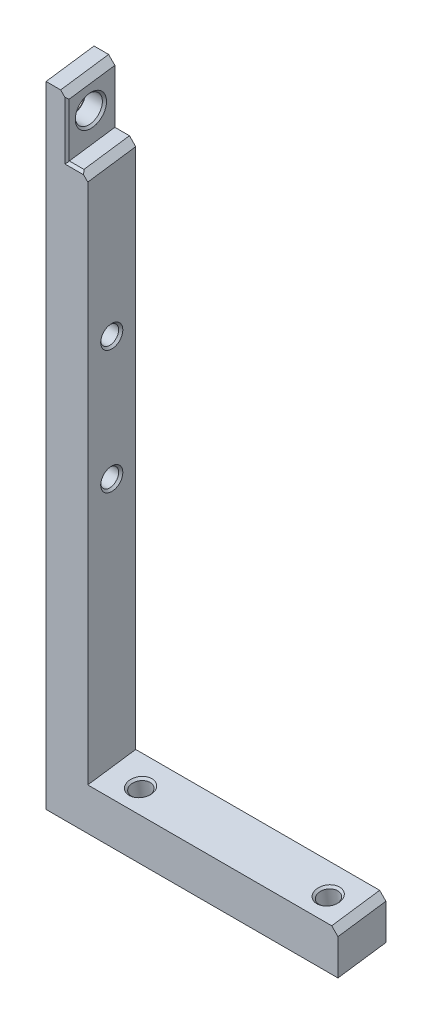
SolidWorks part; units mm, degrees
ref_plane "Top" through (0, 0, 0) normal (0, 0, 1) x (1, 0, 0)
ref_plane "Front" through (0, 0, 0) normal (0, 1, 0) x (1, 0, 0)
ref_plane "Right" through (0, 0, 0) normal (1, 0, 0) x (0, 0, -1)
sketch "Sketch4" plane through (0, 0, 0) normal (1, 0, 0) x (0, 0, -1)
  line L1 (0, 0) -> (11.5, 0)
  line L2 (0, 0) -> (0, 144)
  line L3 (0, 144) -> (11.5, 144)
  line L4 (11.5, 0) -> (11.5, 144)
  dimension "D1" = 11.5
  dimension "D2" = 144
extrude "Boss-Extrude2" add sketch "Sketch4" along normal blind 10
sketch "Sketch6" plane through (10, 0, 0) normal (1, 0, 0) x (0, 0, -1)
  line L0 (5.75, 0) -> (11.5, 0.8081)
  line L1 (0, 0) -> (11.5, 0) construction
  line L2 (11.5, 0) -> (11.5, 144) construction
  line L3 (11.5, 0.8081) -> (10.1083, 10.7108)
  line L4 (10.1083, 10.7108) -> (0.2056, 9.3191)
  line L5 (0.2056, 9.3191) -> (1.5973, -0.5836)
  line L6 (1.5973, -0.5836) -> (5.75, 0)
  line L7 (0, 144) -> (0, 0) construction
  dimension "D1" = 10
  dimension "D2" = 10
  dimension "D3" = 82
extrude "Boss-Extrude3" add sketch "Sketch6" along normal blind 60 and the other way blind 10
sketch "Sketch7" plane through (10, 0, 0) normal (1, 0, 0) x (0, 0, -1)
  line L0 (-3.1126, -1.2456) -> (11.8209, -3.029)
  line L2 (11.8209, -3.029) -> (11.8209, 0.8532)
  line L3 (11.8209, 0.8532) -> (-3.1126, -1.2456)
  line L4 (1.5973, -0.5836) -> (11.5, 0.8081) construction
extrude "Cut-Extrude2" cut sketch "Sketch7" against normal blind 10
sketch "Sketch8" plane through (0, 9.1102, 1.2804) normal (0, 0.9903, 0.1392) x (1, 0, 0)
  line L0 (10, 1.5005) -> (70, 1.5005) construction
  line L1 (70, 11.5005) -> (70, 1.5005) construction
  circle A0 centre (62.5, 6.5005) radius 2.25
  circle A1 centre (17.5, 6.5005) radius 2.25
  dimension "D2" = 4.5
  dimension "D3" = 4.5
  dimension "D1" = 45
  dimension "D4" = 5
  dimension "D5" = 7.5
extrude "Cut-Extrude3" cut sketch "Sketch8" against normal blind 10
sketch "Sketch11" plane through (0, 9.1102, 1.2804) normal (0, 0.9903, 0.1392) x (1, 0, 0)
  line L0 (13.5, 6.5005) -> (13.5, 0)
  line L1 (13.5, 0) -> (21.5, 0)
  line L3 (21.5, 0) -> (21.5, 6.5005)
  line L4 (10, 0) -> (0, 0) construction
  circle A0 centre (17.5, 6.5005) radius 4 construction
  arc A1 (21.5, 6.5005) -> (13.5, 6.5005) centre (17.5, 6.5005) ccw
  dimension "D1" = 8
sketch "Sketch12" plane through (70, 0, 0) normal (1, 0, 0) x (0, 0, -1)
  line L5 (0.2056, 9.3191) -> (10.1083, 10.7108) construction
  line L13 (1.5973, -0.5836) -> (0, -0.8081)
  line L14 (0, -0.8081) -> (0, 9.2902)
  line L16 (1.5973, -0.5836) -> (11.5, 0.8081) construction
  line L17 (0, 144) -> (0, 0) construction
  line L18 (11.5, 0.8081) -> (11.5, 10.9064)
  line L20 (11.5, 10.9064) -> (10.1083, 10.7108)
  line L21 (10.1083, 10.7108) -> (11.5, 0.8081)
  line L22 (10.1083, 10.7108) -> (0.2056, 9.3191) construction
  line L23 (11.5, 0.8081) -> (11.5, 144) construction
  line L25 (11.5, 0.8081) -> (10.1083, 10.7108) construction
  line L26 (0, 9.2902) -> (0.2056, 9.3191)
  line L27 (0.2056, 9.3191) -> (1.5973, -0.5836)
  line L28 (0.2056, 9.3191) -> (1.5973, -0.5836) construction
extrude "Boss-Extrude4" add sketch "Sketch12" against normal up to surface (70 mm away) up to face at (0, 48.0374, -4.3521)
sketch "Sketch13" plane through (10, 0, 0) normal (1, 0, 0) x (0, 0, -1)
  line L0 (11.5, 144) -> (11.5, 152)
  line L1 (11.5, 152) -> (0, 150.3838)
  line L2 (0, 150.3838) -> (0, 144)
  line L3 (0, 144) -> (11.5, 144)
  line L4 (11.5, 10.9064) -> (0, 9.2902) construction
  dimension "D1" = 8
extrude "Boss-Extrude5" add sketch "Sketch13" against normal blind 10
sketch "Sketch14" plane through (10, 0, 0) normal (1, 0, 0) x (0, 0, -1)
  line L0 (11.5, 10.9064) -> (11.5, 152) construction
  circle A0 centre (5.75, 144) radius 3.25
  dimension "D2" = 6.5
  dimension "D1" = 8
  dimension "D3" = 5.75
extrude "Cut-Extrude5" cut sketch "Sketch14" against normal blind 10
sketch "Sketch18" plane through (10, 0, 0) normal (1, 0, 0) x (0, 0, -1)
  line L0 (5.75, 99.6) -> (5.75, 70)
  line L1 (11.5, 10.9064) -> (11.5, 152) construction
  dimension "D1" = 5.75
  dimension "D2" = 29.6
  dimension "D3" = 70
hole_wizard "M4 Clearance Hole1" positions "Sketch19" profile "Sketch20" hole size "M4" standard "DIN" end condition through all
sketch "Sketch19" plane through (10, 0, 0) normal (1, 0, 0) x (0, 0, -1)
  point P0 (5.75, 70)
  point P3 (5.75, 99.6)
sketch "Sketch20" plane through (10, 70, -5.75) normal (0, 1, 0) x (0, 0, -1)
  line L0 (0, 0) -> (0, 10)
  line L1 (0, 10) -> (2.15, 10)
  line L2 (2.15, 10) -> (2.15, 0)
  line L5 (2.15, 0) -> (0, 0)
  line L11 (0, -6.35) -> (0, 107.95) construction
  dimension "Thru Hole Dia." = 4.3
  dimension "Thru Hole Depth" = 10
sketch "Sketch24" plane through (10, 0, 0) normal (1, 0, 0) x (0, 0, -1)
  line L0 (11.5, 152) -> (0, 150.3838)
  line L1 (0, 150.3838) -> (0, 136)
  line L2 (0, 150.3838) -> (0, 9.2902) construction
  line L3 (0, 136) -> (11.5, 137.6162)
  line L4 (11.5, 10.9064) -> (11.5, 152) construction
  line L5 (11.5, 137.6162) -> (11.5, 152)
  circle A0 centre (5.75, 144) radius 3.25 construction
  dimension "D1" = 8
extrude "Cut-Extrude7" cut sketch "Sketch24" against normal blind 5
chamfer "Chamfer2" distance 0.5 angle 45 10 edges at (10, 70, -7.9) (0, 70, -7.9) (10, 99.6, -7.9) (0, 99.6, -7.9) (0, 144, -9) (17.5, 9.7018, -2.9288) (17.5, -0.2009, -4.3206) (62.5, 9.7018, -2.9288) (62.5, -0.2009, -4.3206) (5, 144, -9)
chamfer "Chamfer5" distance 0.5 angle 45 2 edges at (7.5, 136, 0) (5, 143.1919, 0) first distance on face at (21.25, 73.7165, 0)
chamfer "Chamfer6" distance 1.5 angle 45 2 edges at (5, 151.227, -6) (10, 136.849, -6.0409)
chamfer "Chamfer7" distance 1.5 angle 45 1 edges at (70, 10.0983, -5.75)
